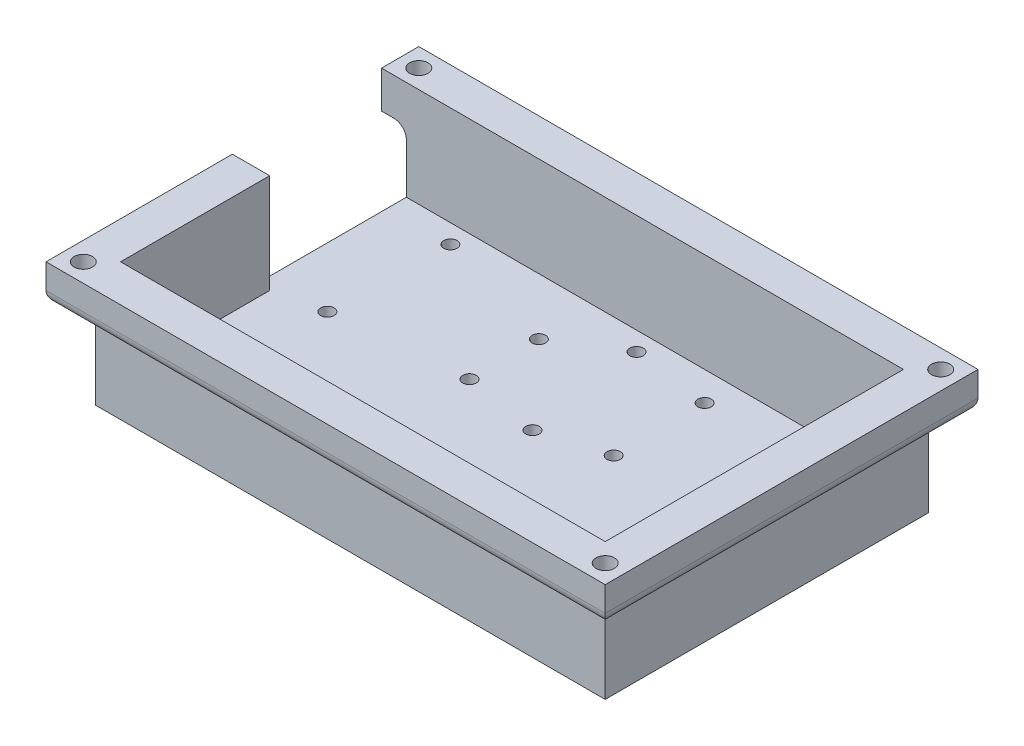
SolidWorks part; units mm, degrees
ref_plane "Front Plane" through (0, 0, 0) normal (0, 0, 1) x (1, 0, 0)
ref_plane "Top Plane" through (0, 0, 0) normal (0, 1, 0) x (1, 0, 0)
ref_plane "Right Plane" through (0, 0, 0) normal (1, 0, 0) x (0, 0, -1)
sketch "Sketch1" plane through (0, 0, 0) normal (0, 1, 0) x (1, 0, 0)
  line L1 (-102.5, 65) -> (102.5, 65)
  line L2 (-102.5, 65) -> (-102.5, -65)
  line L3 (-102.5, -65) -> (102.5, -65)
  line L4 (102.5, 65) -> (102.5, -65)
  line L5 (-102.5, 65) -> (102.5, -65) construction
  line L6 (-102.5, -65) -> (102.5, 65) construction
  point P0 (0, 0)
  dimension "D1" = 130
  dimension "D2" = 205
extrude "Boss-Extrude1" add sketch "Sketch1" along normal blind 10
sketch "Sketch2" plane through (0, 10, 0) normal (0, 1, 0) x (1, 0, 0)
  line L11 (-102.5, 65) -> (102.5, 65)
  line L12 (-102.5, 65) -> (-102.5, -65)
  line L13 (-102.5, -65) -> (102.5, -65)
  line L14 (-97.5, -60) -> (97.5, -60)
  line L15 (97.5, -60) -> (97.5, 60)
  line L16 (-97.5, 60) -> (-97.5, -60)
  line L17 (97.5, 60) -> (-97.5, 60)
  line L18 (-97.5, -60) -> (97.5, -60)
  line L19 (97.5, -60) -> (97.5, 60)
  line L20 (-97.5, 60) -> (-97.5, -60)
  line L21 (97.5, 60) -> (-97.5, 60)
  line L22 (102.5, 65) -> (102.5, -65)
  dimension "D1" = 5
extrude "Boss-Extrude2" add sketch "Sketch2" along normal blind 40
sketch "Sketch3" plane through (0, 10, 0) normal (0, 1, 0) x (1, 0, 0)
  line L0 (-97.5, -60) -> (97.5, -60) construction
  line L1 (-92.5, -55) -> (-2.5, -55)
  line L2 (-92.5, -55) -> (-92.5, -2)
  line L3 (-92.5, -2) -> (-2.5, -2)
  line L4 (-2.5, -55) -> (-2.5, -2)
  line L5 (-84.35, -28.5) -> (-10.65, -28.5) construction
  line L6 (2.5, -2) -> (2.5, -55)
  line L7 (2.5, -55) -> (92.5, -55)
  line L8 (92.5, -55) -> (92.5, -2)
  line L9 (92.5, -2) -> (2.5, -2)
  line L10 (-97.5, 60) -> (-97.5, -60) construction
  line L13 (10.65, -28.5) -> (84.35, -28.5) construction
  circle A0 centre (-84.35, -28.5) radius 2.5
  circle A1 centre (-10.65, -28.5) radius 2.5
  point P4 (-47.5, -2)
  point P12 (-47.5, -28.5)
  point P13 (-92.5, -28.5)
  point P17 (84.35, -28.5)
  point P21 (10.65, -28.5)
  point P25 (2.5, -28.5)
  point P26 (47.5, -2)
  point P27 (47.5, -28.5)
  point P39 (0, 0)
  dimension "D5" = 5
  dimension "D1" = 90
  dimension "D2" = 53
  dimension "D3" = 5
  dimension "D4" = 73.7
  dimension "D6" = 90
  dimension "D7" = 53
  dimension "D8" = 5
  dimension "D9" = 5
  dimension "D10" = 73.7
sketch "Sketch6" plane through (-102.5, 0, 0) normal (-1, 0, 0) x (0, 0, 1)
  line L0 (-65, 50) -> (65, 50) construction
  line L1 (-60, 50) -> (0, 50)
  line L2 (-60, 50) -> (-60, 10)
  line L3 (-60, 10) -> (0, 10)
  line L4 (0, 50) -> (0, 10)
  line L5 (-60, 10) -> (60, 10) construction
extrude "Cut-Extrude1" cut sketch "Sketch6" against normal up to next
sketch "Sketch10" plane through (0, 10, 0) normal (0, 1, 0) x (1, 0, 0)
  line L1 (26, 51.5) -> (69, 51.5)
  line L2 (26, 51.5) -> (26, 8.5)
  line L3 (26, 8.5) -> (69, 8.5)
  line L4 (69, 51.5) -> (69, 8.5)
  line L6 (29.2, 48.3) -> (65.8, 48.3) construction
  line L7 (65.8, 48.3) -> (65.8, 11.7) construction
  line L8 (65.8, 11.7) -> (29.2, 11.7) construction
  line L9 (29.2, 11.7) -> (29.2, 48.3) construction
  line L12 (92.5, -2) -> (2.5, -2) construction
  line L13 (-102.5, 60) -> (-102.5, 0) construction
  point P8 (29.2, 48.3)
  point P9 (65.8, 48.3)
  point P10 (29.2, 11.7)
  point P11 (65.8, 11.7)
  point P14 (47.5, 48.3)
  point P17 (47.5, 8.5)
  point P18 (29.2, 30)
  point P19 (26, 30)
  point P20 (47.5, -2)
  point P21 (-102.5, 30)
  dimension "D1" = 43
  dimension "D2" = 43
  dimension "D5" = 36.6
sketch "Sketch9" plane through (0, 10, 0) normal (0, 1, 0) x (1, 0, 0)
  line L1 (-92.5, 55) -> (9.1, 55)
  line L2 (-92.5, 55) -> (-92.5, 1.7)
  line L3 (-92.5, 1.7) -> (9.1, 1.7)
  line L4 (9.1, 55) -> (9.1, 1.7)
  line L5 (97.5, 60) -> (-102.5, 60) construction
  line L7 (-97.5, 0) -> (-97.5, -60) construction
  point P8 (4.05, 4.2)
  point P9 (-26.4, 9.3)
  point P10 (-26.4, 37.2)
  point P11 (-2.3, 52.4)
  point P12 (-77.2, 52.4)
  point P13 (-78.5, 4.2)
  dimension "D1" = 101.6
  dimension "D2" = 53.3
  dimension "D3" = 5
  dimension "D4" = 2.5
  dimension "D5" = 14
  dimension "D6" = 1.3
  dimension "D7" = 50.8
  dimension "D8" = 24.1
  dimension "D9" = 27.9
  dimension "D10" = 15.2
  dimension "D11" = 5.1
  dimension "D12" = 82.55
  dimension "D13" = 5
hole_wizard "Hole1" positions "Sketch7" profile "Sketch8" legacy
sketch "Sketch7" plane through (0, 10, 0) normal (0, 1, 0) x (1, 0, 0)
  point P0 (-84.35, -28.5)
  point P3 (-10.65, -28.5)
  point P6 (-78.5, 4.2)
  point P9 (-77.2, 52.4)
  point P12 (-26.4, 9.3)
  point P15 (-26.4, 37.2)
  point P18 (-2.3, 52.4)
  point P21 (4.05, 4.2)
  point P25 (29.2, 48.3)
  point P28 (65.8, 48.3)
  point P31 (65.8, 11.7)
  point P34 (29.2, 11.7)
  point P38 (10.65, -28.5)
  point P41 (84.35, -28.5)
sketch "Sketch8" plane through (-84.35, 10, 28.5) normal (1, 0, 0) x (0, 0, 1)
  line L0 (0, 0) -> (0, 8)
  line L1 (0, 8) -> (2.4, 8)
  line L2 (2.4, 8) -> (2.4, 6)
  line L3 (2.4, 6) -> (2.7, 6)
  line L4 (2.7, 6) -> (2.7, 0)
  line L5 (2.7, 0) -> (0, 0)
  line L6 (0, 110) -> (0, -10) construction
  dimension "Diameter" = 4.8
  dimension "Depth" = 8
  dimension "C-Bore Diameter" = 5.4
  dimension "C-Bore Depth" = 6
chamfer "Chamfer1" distance 6 distance2 0.3 14 edges at (-84.35, 4, 31.2) (-10.65, 4, 31.2) (-2.3, 4, -49.7) (4.05, 4, -1.5) (-26.4, 4, -6.6) (-26.4, 4, -34.5) (-77.2, 4, -49.7) (-78.5, 4, -1.5) (65.8, 4, -45.6) (29.2, 4, -45.6) (29.2, 4, -9) (65.8, 4, -9) (84.35, 4, 31.2) (10.65, 4, 31.2) first distance on face at (-84.35, 4, 31.2) first distance on face at (-10.65, 4, 31.2) first distance on face at (-2.3, 4, -49.7) first distance on face at (4.05, 4, -1.5) first distance on face at (-26.4, 4, -6.6) first distance on face at (-26.4, 4, -34.5) first distance on face at (-77.2, 4, -49.7) first distance on face at (-78.5, 4, -1.5) first distance on face at (65.8, 4, -45.6) first distance on face at (29.2, 4, -45.6) first distance on face at (29.2, 4, -9) first distance on face at (65.8, 4, -9) first distance on face at (84.35, 4, 31.2) first distance on face at (10.65, 4, 31.2)
sketch "Sketch11" plane through (0, 50, 0) normal (0, 1, 0) x (1, 0, 0)
  line L0 (-112.5, 75) -> (112.5, 75)
  line L1 (112.5, 75) -> (112.5, -75)
  line L2 (112.5, -75) -> (-112.5, -75)
  line L3 (-112.5, -75) -> (-112.5, 0)
  line L4 (-112.5, 0) -> (-102.5, 0)
  line L5 (-102.5, 0) -> (-102.5, -65)
  line L6 (-102.5, -65) -> (102.5, -65)
  line L7 (102.5, -65) -> (102.5, 65)
  line L9 (-112.5, 60) -> (-112.5, 75)
  line L11 (-102.5, 60) -> (-112.5, 60)
  line L12 (-102.5, 60) -> (-102.5, 65)
  line L13 (-102.5, 65) -> (102.5, 65)
  dimension "D1" = 10
  dimension "D2" = 10
  dimension "D3" = 10
  dimension "D4" = 10
  dimension "D5" = 10
extrude "Boss-Extrude3" add sketch "Sketch11" against normal blind 15
fillet "Fillet1" radius 5 9 edges at (-112.5, 35, 37.5) (0, 35, 75) (112.5, 35, 0) (0, 35, -75) (-102.5, 35, -62.5) (0, 35, -65) (102.5, 35, 0) (-102.5, 35, 32.5) (0, 35, 65)
hole_wizard "Hole2" positions "Sketch12" profile "Sketch13" legacy
sketch "Sketch12" plane through (0, 50, 0) normal (0, 1, 0) x (1, 0, 0)
  line L0 (-112.5, 75) -> (-112.5, 60) construction
  line L1 (-97.5, 0) -> (-112.5, 0) construction
  line L3 (-97.5, -60) -> (-97.5, -75) construction
  line L4 (-112.5, -75) -> (112.5, -75) construction
  line L6 (97.5, -60) -> (112.5, -60) construction
  line L7 (112.5, -75) -> (112.5, 75) construction
  point P0 (-105, 67.5)
  point P2 (105, 67.5)
  point P4 (105, -67.5)
  point P6 (-105, -67.5)
  point P11 (-112.5, 67.5)
  point P18 (-105, 0)
  point P27 (-97.5, -67.5)
  point P37 (105, -60)
sketch "Sketch13" plane through (-105, 50, -67.5) normal (1, 0, 0) x (0, 0, 1)
  line L0 (0, 0) -> (0, 10)
  line L1 (0, 10) -> (3.4, 10)
  line L2 (3.4, 10) -> (3.4, 6)
  line L3 (3.4, 6) -> (3.7, 6)
  line L4 (3.7, 6) -> (3.7, 0)
  line L5 (3.7, 0) -> (0, 0)
  line L6 (0, 110) -> (0, -10) construction
  dimension "Diameter" = 6.8
  dimension "Depth" = 10
  dimension "C-Bore Diameter" = 7.4
  dimension "C-Bore Depth" = 6
chamfer "Chamfer2" distance 6 distance2 0.3 4 edges at (-105, 44, 71.2) (105, 44, 71.2) (105, 44, -63.8) (-105, 44, -63.8) first distance on face at (-105, 44, 71.2) first distance on face at (105, 44, 71.2) first distance on face at (105, 44, -63.8) first distance on face at (-105, 44, -63.8)
